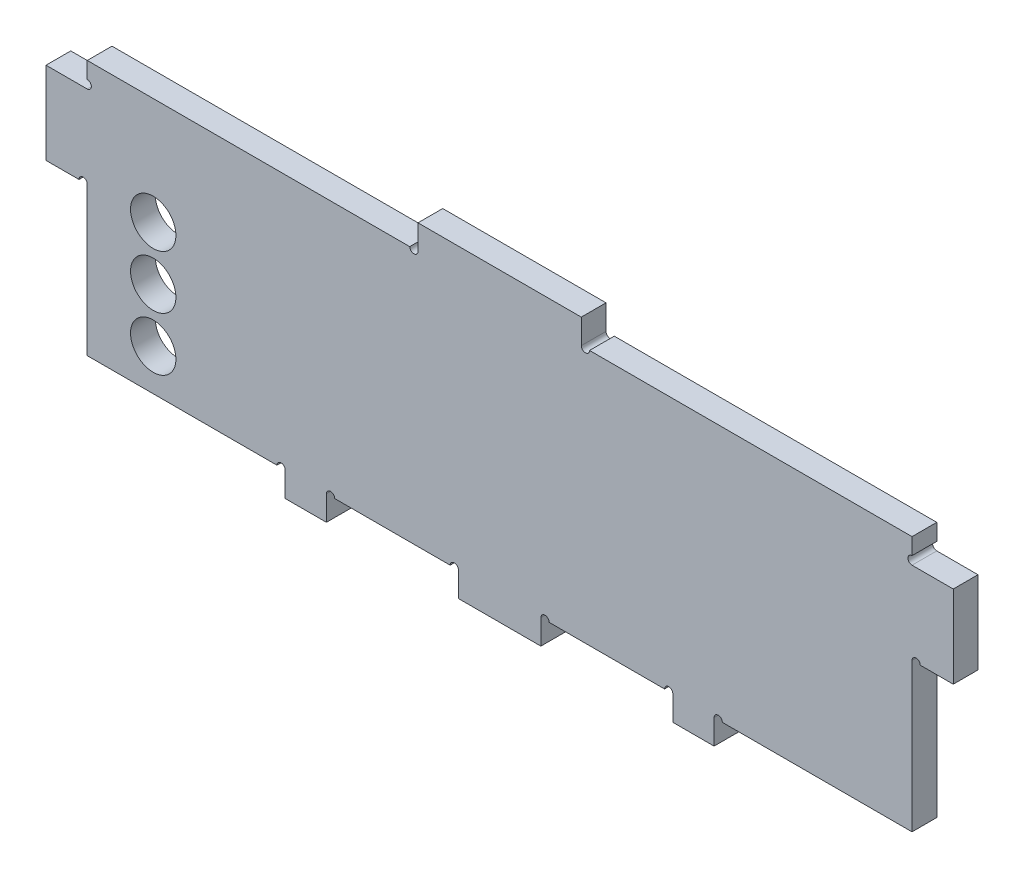
SolidWorks part; units mm, degrees
ref_plane "Front Plane" through (0, 0, 0) normal (0, 0, 1) x (1, 0, 0)
ref_plane "Top Plane" through (0, 0, 0) normal (0, 1, 0) x (1, 0, 0)
ref_plane "Right Plane" through (0, 0, 0) normal (1, 0, 0) x (0, 0, -1)
sketch "Sketch1" plane through (0, 0, 0) normal (0, 0, 1) x (1, 0, 0)
  line L0 (-5, 0) -> (5, 0)
  line L1 (5, 0) -> (5, 3)
  line L2 (5, 3) -> (21, 3)
  line L3 (21, 3) -> (21, 0)
  line L4 (21, 0) -> (26, 0)
  line L5 (26, 0) -> (26, 3)
  line L6 (26, 3) -> (50, 3)
  line L8 (50, 3) -> (50, 21)
  line L9 (50, 21) -> (55, 21)
  line L10 (55, 21) -> (55, 31)
  line L11 (55, 31) -> (50, 31)
  line L12 (50, 34) -> (0, 34)
  line L13 (0, 34) -> (0, 0) construction
  line L14 (-50, 34) -> (0, 34)
  line L15 (-5, 0) -> (-5, 3)
  line L16 (-5, 3) -> (-21, 3)
  line L17 (-21, 3) -> (-21, 0)
  line L18 (-21, 0) -> (-26, 0)
  line L19 (-26, 0) -> (-26, 3)
  line L20 (-26, 3) -> (-50, 3)
  line L21 (-42, 21) -> (-42, 8) construction
  line L22 (-50, 3) -> (-50, 21)
  line L23 (-50, 21) -> (-55, 21)
  line L24 (-55, 21) -> (-55, 31)
  line L25 (-50, 31) -> (-50, 34)
  line L26 (50, 31) -> (50, 34)
  line L27 (-55, 31) -> (-50, 31)
  circle A4 centre (-42, 8) radius 2.75
  circle A5 centre (-42, 14.5) radius 2.75
  circle A6 centre (-42, 21) radius 2.75
  dimension "D13" = 5.5
  dimension "D11" = 8
  dimension "D1" = 5
  dimension "D2" = 5
  dimension "D3" = 3
  dimension "D4" = 16
  dimension "D5" = 55
  dimension "D6" = 5
  dimension "D7" = 5
  dimension "D8" = 10
  dimension "D9" = 31
  dimension "D10" = 3
  dimension "D12" = 5
  dimension "D14" = 13
extrude "Boss-Extrude1" add sketch "Sketch1" along normal blind 3
sketch "Sketch4" plane through (0, 0, 3) normal (0, 0, 1) x (1, 0, 0)
  line L0 (-50, 34) -> (0, 34) construction
  line L1 (-9.9, 34) -> (9.9, 34)
  line L2 (-9.9, 34) -> (-9.9, 37)
  line L3 (-9.9, 37) -> (9.9, 37)
  line L4 (9.9, 34) -> (9.9, 37)
  dimension "D1" = 3
  dimension "D2" = 19.8
extrude "Boss-Extrude2" add sketch "Sketch4" against normal blind 3
sketch "Sketch3" plane through (0, 0, 3) normal (0, 0, 1) x (1, 0, 0)
  line L0 (5, 3) -> (21, 3) construction
  line L1 (26, 3) -> (50, 3) construction
  line L2 (50, 34) -> (0, 34) construction
  line L3 (50, 21) -> (55, 21) construction
  line L4 (-50, 34) -> (0, 34) construction
  line L5 (0, 34) -> (0, 0) construction
  arc A0 (5, 3) -> (6, 3) centre (5.5, 3) cw
  arc A1 (21, 3) -> (20, 3) centre (20.5, 3) ccw
  arc A2 (26, 3) -> (27, 3) centre (26.5, 3) cw
  arc A3 (50, 21) -> (51, 21) centre (50.5, 21) cw
  arc A4 (50, 31) -> (50, 32) centre (50, 31.5) cw
  arc A5 (-50, 31) -> (-50, 32) centre (-50, 31.5) ccw
  arc A6 (-50, 21) -> (-51, 21) centre (-50.5, 21) ccw
  arc A7 (-26, 3) -> (-27, 3) centre (-26.5, 3) ccw
  arc A8 (-21, 3) -> (-20, 3) centre (-20.5, 3) cw
  arc A9 (-5, 3) -> (-6, 3) centre (-5.5, 3) ccw
  arc A10 (9.9, 34) -> (10.9, 34) centre (10.4, 34) ccw
  arc A11 (-9.9, 34) -> (-10.9, 34) centre (-10.4, 34) cw
  line M4 (5, 3) -> (21, 3)
  line M8 (26, 3) -> (50, 3)
  line M11 (50, 21) -> (55, 21)
  line M14 (50, 31) -> (50, 34)
  line M15 (50, 34) -> (9.9, 34)
  line M16 (-50, 34) -> (-50, 31)
  line M19 (-55, 21) -> (-50, 21)
  line M22 (-50, 3) -> (-26, 3)
  line M26 (-21, 3) -> (-5, 3)
  line M60 (-9.9, 34) -> (-50, 34)
  dimension "D1" = 0.5
extrude "Cut-Extrude2" cut sketch "Sketch3" against normal through all contours A4 M14 | A3 M11 | A5 M16 | A6 M19 | A7 M22 | A8 M26 | A9 M26 | A0 M4 | A1 M4 | A2 M8 | A11 M60 | A10 M15 region at (20.5, 3.2122, 3) region at (5.5, 3.2122, 3) region at (26.5, 3.2122, 3) region at (50.5, 21.2122, 3) region at (10.4, 33.7878, 3) region at (49.7878, 31.5, 3) region at (-49.7878, 31.5, 3) region at (-10.4, 33.7878, 3) region at (-50.5, 21.2122, 3) region at (-26.5, 3.2122, 3) region at (-5.5, 3.2122, 3) region at (-20.5, 3.2122, 3)
